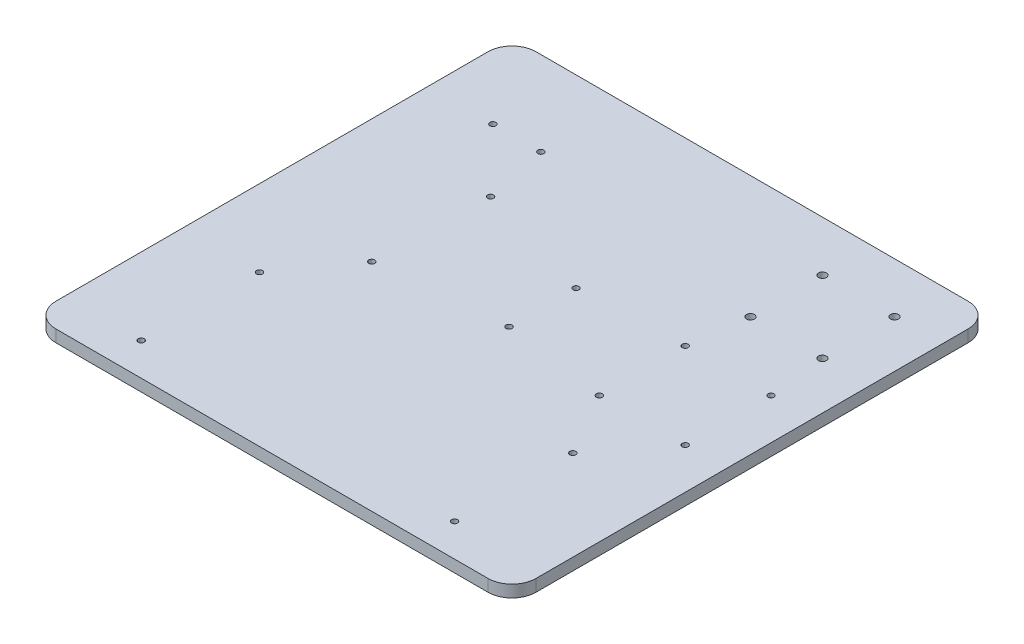
SolidWorks part; units mm, degrees
ref_plane "Front Plane" through (0, 0, 0) normal (0, 0, 1) x (1, 0, 0)
ref_plane "Top Plane" through (0, 0, 0) normal (0, 1, 0) x (1, 0, 0)
ref_plane "Right Plane" through (0, 0, 0) normal (1, 0, 0) x (0, 0, -1)
sketch "Sketch1" plane through (0, 0, 0) normal (0, 1, 0) x (1, 0, 0)
  line L1 (-90, -100) -> (90, -100)
  line L2 (-100, -90) -> (-100, 90)
  line L3 (-90, 100) -> (90, 100)
  line L4 (100, -90) -> (100, 90)
  line L5 (-100, -100) -> (100, 100) construction
  line L6 (-100, 100) -> (100, -100) construction
  arc A0 (90, -100) -> (100, -90) centre (90, -90) ccw
  arc A1 (-90, -100) -> (-100, -90) centre (-90, -90) cw
  arc A2 (-100, 90) -> (-90, 100) centre (-90, 90) cw
  arc A3 (90, 100) -> (100, 90) centre (90, 90) cw
  point P1 (0, 0)
  dimension "D3" = 10
  dimension "D1" = 200
  dimension "D2" = 200
extrude "Boss-Extrude1" add sketch "Sketch1" along normal blind 5 contours L2 A2 L3 A3 L4 A0 L1 A1
hole_wizard "arduino uno holes" positions "Sketch3" profile "Sketch2" tap size "M3x0.5" standard "ANSI Metric" end condition through all
sketch "Sketch3" plane through (0, 5, 0) normal (0, 1, 0) x (1, 0, 0)
  point P0 (3.609, 23.0549)
  point P2 (3.609, -4.8451)
  point P4 (-47.191, 38.2549)
  point P6 (-48.491, -9.9451)
  dimension "D1" = 27.9
  dimension "D2" = 15.2
  dimension "D3" = 50.8
  dimension "D4" = 1.3
  dimension "D5" = 5.1
sketch "Sketch2" plane through (3.609, 5, -23.0549) normal (1, 0, 0) x (0, 0, 1)
  line L0 (0, 0) -> (0, 5)
  line L1 (0, 5) -> (1.25, 5)
  line L2 (1.25, 5) -> (1.25, 0)
  line L5 (1.25, 0) -> (0, 0)
  line L11 (0, -6.35) -> (0, 107.95) construction
  dimension "Thru Tap Drill Dia." = 2.5
  dimension "Thru Tap Drill Depth" = 5
cosmetic thread "Hole Thread1" parameters "D2"=3
cosmetic thread "Hole Thread2" parameters "D2"=3
cosmetic thread "Hole Thread3" parameters "D2"=3
cosmetic thread "Hole Thread4" parameters "D2"=3
hole_wizard "relay board holes" positions "Sketch14" profile "Sketch15" tap size "M3x0.5" standard "ANSI Metric" end condition through all
sketch "Sketch14" plane through (0, 5, 0) normal (0, 1, 0) x (1, 0, 0)
  point P0 (-68.0545, -86.3793)
  point P7 (62.4455, -86.3793)
  point P8 (62.4455, -37.1293)
  point P9 (-68.0545, -37.1293)
  dimension "D1" = 2
  dimension "D2" = 2
sketch "Sketch15" plane through (-68.0545, 5, 86.3793) normal (1, 0, 0) x (0, 0, 1)
  line L0 (0, 0) -> (0, 5)
  line L1 (0, 5) -> (1.25, 5)
  line L2 (1.25, 5) -> (1.25, 0)
  line L5 (1.25, 0) -> (0, 0)
  line L11 (0, -6.35) -> (0, 107.95) construction
  dimension "Thru Tap Drill Dia." = 2.5
  dimension "Thru Tap Drill Depth" = 5
cosmetic thread "Hole Thread21" parameters "D2"=3
cosmetic thread "Hole Thread22" parameters "D2"=3
cosmetic thread "Hole Thread23" parameters "D2"=3
cosmetic thread "Hole Thread24" parameters "D2"=3
hole_wizard "l298n holes" positions "Sketch16" profile "Sketch17" tap size "M3x0.5" standard "ANSI Metric" end condition through all
sketch "Sketch16" plane through (0, 5, 0) normal (0, 1, 0) x (1, 0, 0)
  point P0 (47.2019, -10.8221)
  point P6 (82.9619, -10.8221)
  point P7 (82.9619, 24.9379)
  point P8 (47.2019, 24.9379)
  dimension "D1" = 2
  dimension "D2" = 2
sketch "Sketch17" plane through (47.2019, 5, 10.8221) normal (1, 0, 0) x (0, 0, 1)
  line L0 (0, 0) -> (0, 5)
  line L1 (0, 5) -> (1.25, 5)
  line L2 (1.25, 5) -> (1.25, 0)
  line L5 (1.25, 0) -> (0, 0)
  line L11 (0, -6.35) -> (0, 107.95) construction
  dimension "Thru Tap Drill Dia." = 2.5
  dimension "Thru Tap Drill Depth" = 5
cosmetic thread "Hole Thread25" parameters "D2"=3
cosmetic thread "Hole Thread26" parameters "D2"=3
cosmetic thread "Hole Thread27" parameters "D2"=3
cosmetic thread "Hole Thread28" parameters "D2"=3
hole_wizard "motor mounting bracket holes" positions "Sketch18" profile "Sketch19" tap size "M4x0.7" standard "ANSI Metric" end condition through all
sketch "Sketch18" plane through (0, 5, 0) normal (0, 1, 0) x (1, 0, 0)
  point P0 (50.273, 49.0431)
  point P5 (80.273, 49.0431)
  point P6 (80.273, 79.0431)
  point P7 (50.273, 79.0431)
  dimension "D1" = 2
  dimension "D2" = 2
sketch "Sketch19" plane through (50.273, 5, -49.0431) normal (1, 0, 0) x (0, 0, 1)
  line L0 (0, 0) -> (0, 5)
  line L1 (0, 5) -> (1.65, 5)
  line L2 (1.65, 5) -> (1.65, 0)
  line L5 (1.65, 0) -> (0, 0)
  line L11 (0, -6.35) -> (0, 107.95) construction
  dimension "Thru Tap Drill Dia." = 3.3
  dimension "Thru Tap Drill Depth" = 5
cosmetic thread "Hole Thread29" parameters "D2"=4
cosmetic thread "Hole Thread30" parameters "D2"=4
cosmetic thread "Hole Thread31" parameters "D2"=4
cosmetic thread "Hole Thread32" parameters "D2"=4
hole_wizard "bt mount holes" positions "Sketch20" profile "Sketch21" tap size "M3x0.5" standard "ANSI Metric" end condition through all
sketch "Sketch20" plane through (0, 5, 0) normal (0, 1, 0) x (1, 0, 0)
  point P0 (-72.8746, 64.9008)
  point P2 (-52.8746, 64.9008)
  dimension "D1" = 20
sketch "Sketch21" plane through (-72.8746, 5, -64.9008) normal (1, 0, 0) x (0, 0, 1)
  line L0 (0, 0) -> (0, 5)
  line L1 (0, 5) -> (1.25, 5)
  line L2 (1.25, 5) -> (1.25, 0)
  line L5 (1.25, 0) -> (0, 0)
  line L11 (0, -6.35) -> (0, 107.95) construction
  dimension "Thru Tap Drill Dia." = 2.5
  dimension "Thru Tap Drill Depth" = 5
cosmetic thread "Hole Thread33" parameters "D2"=3
cosmetic thread "Hole Thread34" parameters "D2"=3
equation "\"w\"= 200"
equation "\"D1@Sketch1\"=\"w\""
equation "\"h\" = 200"
equation "\"D2@Sketch1\"=\"h\""
equation "\"th\"=5"
equation "\"D1@Boss-Extrude1\"=\"th\""
